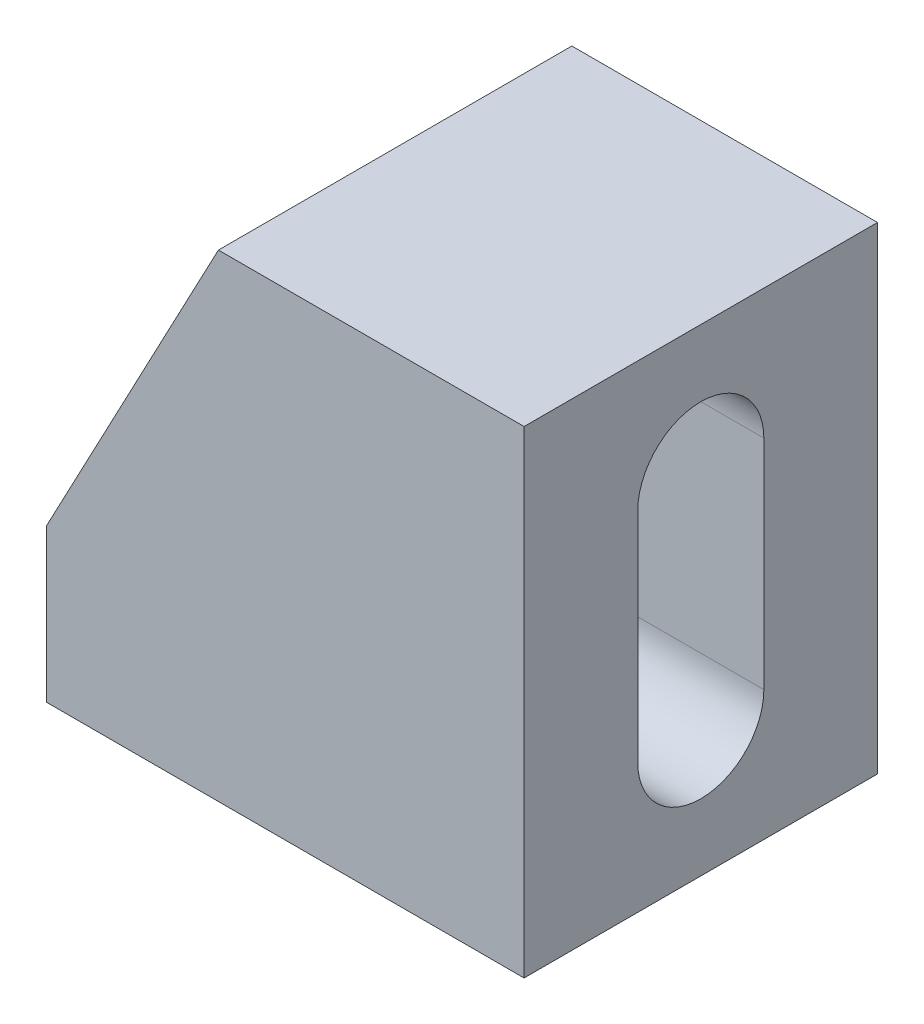
SolidWorks part; units mm, degrees
ref_plane "Front Plane" through (0, 0, 0) normal (0, 0, 1) x (1, 0, 0)
ref_plane "Top Plane" through (0, 0, 0) normal (0, 1, 0) x (1, 0, 0)
ref_plane "Right Plane" through (0, 0, 0) normal (1, 0, 0) x (0, 0, -1)
sketch "Sketch2" plane through (0, 0, 0) normal (0, 0, 1) x (1, 0, 0)
  line L0 (0, 0) -> (0, 8)
  line L1 (0, 8) -> (9, 25)
  line L2 (9, 25) -> (25, 25)
  line L3 (25, 25) -> (25, 0)
  line L4 (25, 0) -> (0, 0)
  dimension "D1" = 25
  dimension "D2" = 25
  dimension "D3" = 16
  dimension "D4" = 8
extrude "Boss-Extrude2" add sketch "Sketch2" along normal mid plane 18.5
hole_wizard "M6 Clearance Slot1" positions "Sketch3" profile "Sketch4" size "M6" standard "ISO" slot yes end condition through all
sketch "Sketch3" plane through (25, 0, 0) normal (1, 0, 0) x (0, 0, -1)
  line L0 (0, 3.5) -> (0, 21.5) construction
  line L1 (-9.25, 12.5) -> (0, 12.5) construction
  line L2 (-9.25, 0) -> (-9.25, 25) construction
  line L4 (0, 0) -> (0, 3.5) construction
  line L5 (-9.25, 0) -> (9.25, 0) construction
  point P0 (0, 12.5)
  dimension "D1" = 18
sketch "Sketch4" plane through (25, 12.5, 0) normal (0, 1, 0) x (0, 0, -1)
  line L0 (0, 0) -> (0, 25)
  line L1 (0, 25) -> (3.3, 25)
  line L2 (3.3, 25) -> (3.3, 0)
  line L5 (3.3, 0) -> (0, 0)
  line L11 (0, -6.35) -> (0, 107.95) construction
  dimension "Thru Hole Dia." = 6.6
  dimension "Thru Hole Depth" = 25
